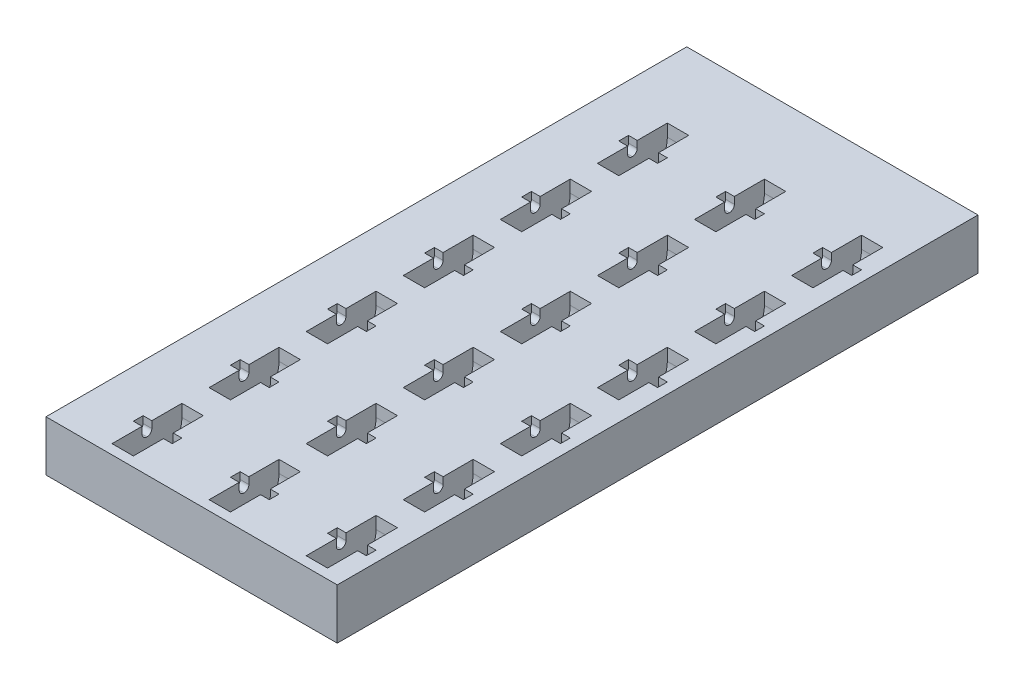
SolidWorks part; units mm, degrees
ref_plane "Front Plane" through (0, 0, 0) normal (0, 0, 1) x (1, 0, 0)
ref_plane "Top Plane" through (0, 0, 0) normal (0, 1, 0) x (1, 0, 0)
ref_plane "Right Plane" through (0, 0, 0) normal (1, 0, 0) x (0, 0, -1)
sketch "Sketch1" plane through (0, 0, 0) normal (0, 1, 0) x (1, 0, 0)
  line L1 (-75, -165) -> (75, -165)
  line L2 (-75, -165) -> (-75, 165)
  line L3 (-75, 165) -> (75, 165)
  line L4 (75, -165) -> (75, 165)
  line L5 (-75, -165) -> (75, 165) construction
  line L6 (-75, 165) -> (75, -165) construction
  point P0 (0, 0)
  dimension "D1" = 150
extrude "Boss-Extrude1" add sketch "Sketch1" along normal blind 26
sketch "Sketch2" plane through (0, 26, 0) normal (0, 1, 0) x (1, 0, 0)
  line L0 (-75, -165) -> (75, -165) construction
  line L5 (54, -160) -> (65, -160)
  line L6 (54, -160) -> (54, -124)
  line L11 (54, -124) -> (65, -124)
  line L12 (65, -160) -> (65, -124)
  line L13 (54, -160) -> (65, -124) construction
  line L14 (54, -124) -> (65, -160) construction
  line L15 (75, -165) -> (75, 165) construction
  point P0 (59.5, -142)
  point P1 (0, 0)
  dimension "D1" = 36
  dimension "D2" = 5
  dimension "D3" = 11
  dimension "D4" = 10
extrude "Cut-Extrude1" cut sketch "Sketch2" against normal blind 22 contours L5 L12 L11 L6 | L6 L5 L12 L11 region at (59.5, 26, 142)
sketch "Sketch3" plane through (0, 26, 0) normal (0, 1, 0) x (1, 0, 0)
  line L0 (54, -142) -> (65, -142) construction
  line L4 (49.5, -144.5) -> (69.5, -144.5)
  line L5 (49.5, -144.5) -> (49.5, -139.5)
  line L6 (49.5, -139.5) -> (69.5, -139.5)
  line L7 (69.5, -144.5) -> (69.5, -139.5)
  line L8 (49.5, -144.5) -> (69.5, -139.5) construction
  line L9 (49.5, -139.5) -> (69.5, -144.5) construction
  line L10 (54, -160) -> (54, -124) construction
  line L11 (65, -160) -> (65, -124) construction
  point P2 (34.6568, -142)
  point P4 (54.1252, -144.0475)
  point P5 (0, 0)
  point P6 (59.5, -142)
  point P11 (0, 0)
  point P13 (45.6568, -142)
  dimension "D1" = 5
  dimension "D2" = 20
extrude "Cut-Extrude2" cut sketch "Sketch3" against normal blind 6
fillet "Fillet1" radius 15.7 2 edges at (59.5, 4, 160) (59.5, 4, 124)
fillet "Fillet2" radius 2.5 4 edges at (51.75, 20, 144.5) (51.75, 20, 139.5) (67.25, 20, 144.5) (67.25, 20, 139.5)
pattern_linear "LPattern1" count 3 spacing 50 along (-1, 0, 0) count 6 spacing 50 along (0, 0, -1) of "Cut-Extrude1", "Cut-Extrude2", "Fillet1", "Fillet2"
